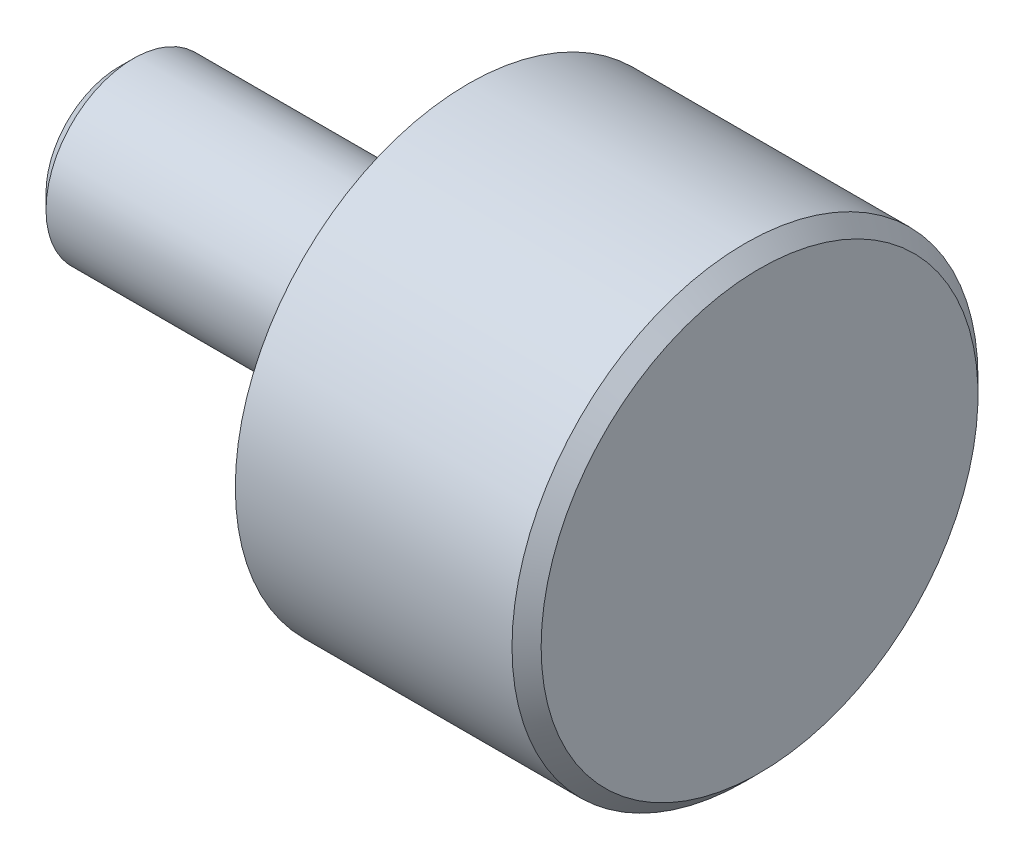
SolidWorks part; units mm, degrees
material "AISI 1045 Steel, cold drawn"
ref_plane "Front Plane" through (0, 0, 0) normal (0, 0, 1) x (1, 0, 0)
ref_plane "Top Plane" through (0, 0, 0) normal (0, 1, 0) x (1, 0, 0)
ref_plane "Right Plane" through (0, 0, 0) normal (1, 0, 0) x (0, 0, -1)
other "Configuration Table"
sketch "Sketch_Tip_Profile" plane through (0, 0, 0) normal (0, 0, 1) x (1, 0, 0)
  line L0 (-15, 0) -> (15, 0) construction
  line L1 (-12, 0) -> (-12, 2.5)
  line L2 (-12, 2.5) -> (-11.5, 3)
  line L3 (-11.5, 3) -> (0, 3)
  line L4 (0, 3) -> (0, 8)
  line L5 (0, 8) -> (9.5, 8)
  line L6 (9.5, 8) -> (10, 7.5)
  line L7 (10, 7.5) -> (10, 0)
  line L8 (10, 0) -> (-12, 0)
revolve "Tip_Revolve_D16x10_Stud_M6x12" add sketch "Sketch_Tip_Profile" angle 360 about L0
ref_axis "Shaft_Axis_X" through (106.7263, 0, 0) along (-1, 0, 0)
